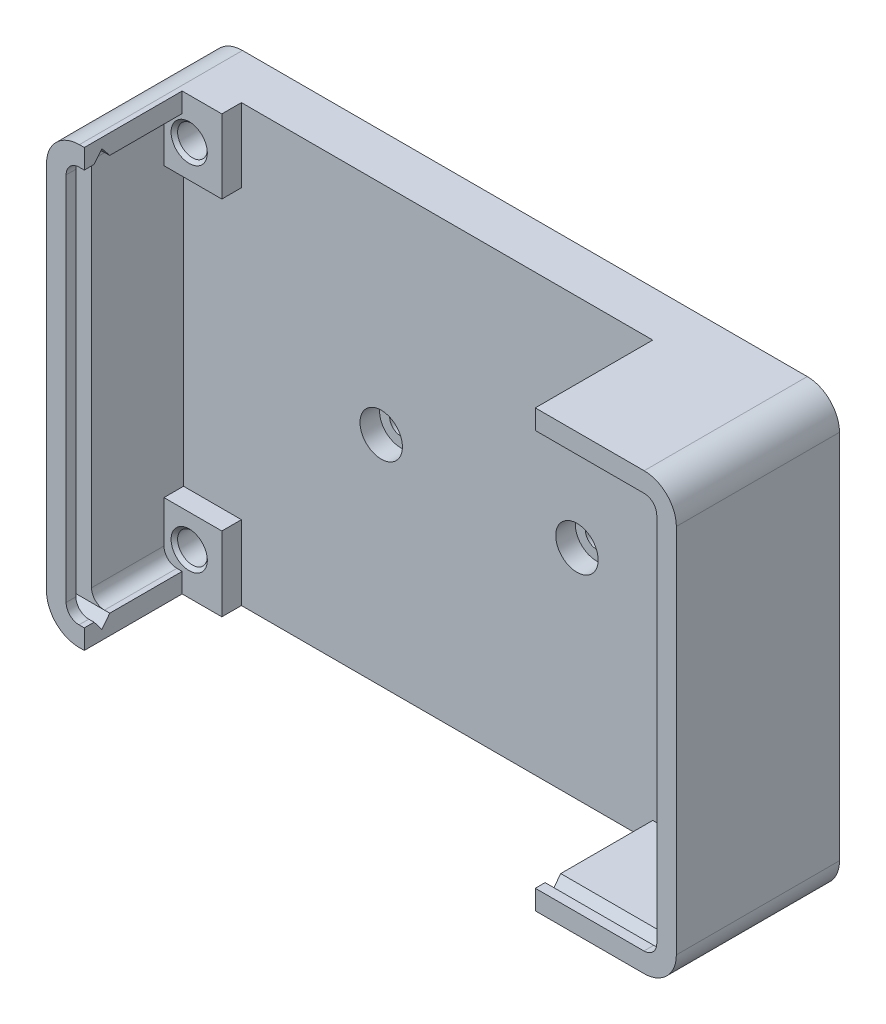
SolidWorks part; units mm, degrees
note: The reader was unsure of these and kept them because the rebuilt part matched: shared geometry of "Sketch1<4>".
ref_plane "Front Plane" through (0, 0, 0) normal (0, 0, 1) x (1, 0, 0)
ref_plane "Top Plane" through (0, 0, 0) normal (0, 1, 0) x (1, 0, 0)
ref_plane "Right Plane" through (0, 0, 0) normal (1, 0, 0) x (0, 0, -1)
sketch "Sketch1" plane through (0, 0, -11.1517) normal (0, 0, -1) x (-1, 0, 0)
  line L0 (-25.2167, 125.2267) -> (-25.2167, 68.4777)
  line L1 (-22.2167, 125.2267) -> (-22.2167, 68.4777)
  line L26 (-27.2482, 127.2583) -> (-113.8062, 127.2583)
  line L28 (-27.2482, 130.2583) -> (-113.8062, 130.2583)
  line L29 (-118.7416, 125.3228) -> (-118.7416, 68.4638)
  line L30 (-113.7774, 63.4996) -> (-27.1948, 63.4996)
  line L39 (-115.7416, 125.3228) -> (-115.7416, 68.4638)
  line L40 (-113.7774, 66.4996) -> (-27.1948, 66.4996)
  line L42 (-22.2167, 68.4777) -> (-22.2167, 125.2267) construction
  line L43 (-25.2167, 68.4777) -> (-25.2167, 125.2267) construction
  arc A20 (-113.8062, 127.2583) -> (-115.7416, 125.3228) centre (-113.8062, 125.3228) ccw
  arc A21 (-113.8062, 130.2583) -> (-118.7416, 125.3228) centre (-113.8062, 125.3228) ccw
  arc A22 (-118.7416, 68.4638) -> (-113.7774, 63.4996) centre (-113.7774, 68.4638) ccw
  arc A23 (-27.1948, 63.4996) -> (-22.2167, 68.4777) centre (-27.1948, 68.4777) ccw
  arc A28 (-27.1948, 66.4996) -> (-25.2167, 68.4777) centre (-27.1948, 68.4777) ccw
  arc A29 (-25.2167, 125.2267) -> (-27.2482, 127.2583) centre (-27.2482, 125.2267) ccw
  arc A31 (-115.7416, 68.4638) -> (-113.7774, 66.4996) centre (-113.7774, 68.4638) ccw
  arc A32 (-22.2167, 125.2267) -> (-27.2482, 130.2583) centre (-27.2482, 125.2267) ccw
  dimension "D2" = 3
  dimension "D3" = 0.3
  dimension "D1" = 0.3
extrude "Boss-Extrude1" add sketch "Sketch1" against normal blind 7
extrude "Boss-Extrude2" add sketch "Sketch1<4>" against normal blind 25
sketch "Sketch1<4>" plane through (0, 0, -11.1517) normal (0, 0, -1) x (-1, 0, 0) same geometry as "Sketch1"
sketch "Sketch2" plane through (0, 0, -4.1517) normal (0, 0, 1) x (1, 0, 0)
  circle A0 centre (111.633, 123.952) radius 2.275
  circle A1 centre (111.633, 69.901) radius 2.275
  circle A2 centre (29.083, 69.901) radius 2.275
  circle A3 centre (29.083, 123.952) radius 2.275
  dimension "D1" = 4.55
extrude "Cut-Extrude1" cut sketch "Sketch2" against normal blind 6
sketch "Sketch3" plane through (0, 0, -4.1517) normal (0, 0, 1) x (1, 0, 0)
  line L0 (70.5272, 127.2583) -> (70.4861, 66.4996) construction
  line L1 (27.2482, 127.2583) -> (113.8062, 127.2583) construction
  line L2 (113.7774, 66.4996) -> (27.1948, 66.4996) construction
  point P1 (85.5067, 96.8789)
  point P8 (70.5067, 96.8789)
  point P9 (55.5067, 96.8992)
  dimension "D1" = 15
hole_wizard "CBORE for M3 SHCS1" positions "Sketch3" profile "Sketch4" counterbore size "M3" standard "ANSI Metric"
sketch "Sketch4" plane through (55.5067, 96.8992, -4.1517) normal (1, 0, 0) x (0, -1, 0)
  line L0 (0, 0) -> (0, 8.0215)
  line L1 (0, 8.0215) -> (1.7, 7)
  line L2 (1.7, 7) -> (1.7, 3)
  line L3 (1.7, 3) -> (3.25, 3)
  line L4 (3.25, 3) -> (3.25, 0)
  line L5 (3.25, 0) -> (0, 0)
  line L10 (0, 8.0215) -> (-1.7, 7) construction
  line L11 (0, -6.35) -> (0, 107.95) construction
  dimension "Hole Dia." = 3.4
  dimension "Hole Depth" = 7
  dimension "C'Bore Dia." = 6.5
  dimension "C'Bore Depth" = 3
  dimension "Drill Angle" = 118
ref_plane "Plane1" through (0, 96.8789, 0) normal (0, -1, 0) x (-1, 0, 0)
sketch "Sketch5" plane through (0, 96.8789, 0) normal (0, -1, 0) x (-1, 0, 0)
  line L0 (-113.7774, -13.8483) -> (-27.1948, -13.8483) construction
  line L1 (-97.1229, -13.8483) -> (-28.0044, -13.8483)
  line L2 (-97.1229, -13.8483) -> (-97.1229, 4.1517)
  line L3 (-97.1229, 4.1517) -> (-28.0044, 4.1517)
  line L4 (-28.0044, -13.8483) -> (-28.0044, 4.1517)
  line L5 (-33.0044, 1.1706) -> (-33.0044, -5.9294) construction
  line L6 (-72.1229, 1.1706) -> (-72.1229, -5.9294) construction
  line L8 (-113.7774, 4.1517) -> (-27.1948, 4.1517) construction
  dimension "D1" = 5
  dimension "D2" = 25
extrude "Cut-Extrude2" cut sketch "Sketch5" against normal through all both and the other way through all
sketch "Sketch6" plane through (22.2167, -0.0074, 0) normal (-1, 0, 0) x (0, 0, 1)
  line L0 (13.8483, 68.4852) -> (13.8483, 125.2341) construction
  line L1 (9.9483, 128.7657) -> (12.3483, 128.7657)
  line L2 (9.9483, 128.7657) -> (9.9483, 64.9536)
  line L3 (9.9483, 64.9536) -> (12.3483, 64.9536)
  line L4 (12.3483, 128.7657) -> (12.3483, 64.9536)
  line L6 (13.8483, 130.2657) -> (-11.1517, 130.2657) construction
  line L7 (9.9483, 127.2657) -> (11.1483, 128.7657)
  line L8 (13.8483, 127.2657) -> (-4.1517, 127.2657) construction
  line L9 (11.1483, 128.7657) -> (12.3483, 127.2657)
  line L10 (12.3483, 66.507) -> (11.1483, 64.9536)
  line L11 (13.8483, 66.507) -> (-4.1517, 66.507) construction
  line L12 (11.1483, 64.9536) -> (9.9483, 66.507)
  point P4 (13.8483, 96.8596)
  point P7 (12.3483, 96.8596)
  dimension "D1" = 1.5
  dimension "D2" = 2.4
  dimension "D3" = 1.5
extrude "Cut-Extrude3" cut sketch "Sketch6" against normal offset from surface (95.025 mm away) 1.5
sketch "Sketch7" plane through (0, 0, -4.1517) normal (0, 0, 1) x (1, 0, 0)
  line L0 (22.2167, 68.4777) -> (22.2167, 125.2267) construction
  line L1 (28.0044, 130.2583) -> (97.1229, 130.2583) construction
  line L2 (27.2482, 130.2583) -> (28.0044, 130.2583) construction
  line L3 (22.2167, 118.952) -> (22.2167, 125.2267)
  line L4 (28.0044, 130.2583) -> (34.083, 130.2583)
  line L5 (27.2482, 130.2583) -> (28.0044, 130.2583)
  line L6 (34.083, 130.2583) -> (34.083, 118.952)
  line L7 (34.083, 118.952) -> (22.2167, 118.952)
  line L8 (118.7416, 125.3228) -> (118.7416, 68.4638) construction
  line L9 (97.1229, 130.2583) -> (113.8062, 130.2583) construction
  line L10 (118.7416, 125.3228) -> (118.7416, 118.952)
  line L11 (106.633, 130.2583) -> (113.8062, 130.2583)
  line L12 (113.7774, 63.4996) -> (97.1229, 63.4996) construction
  line L13 (113.7774, 63.4996) -> (106.633, 63.4996)
  line L14 (28.0044, 63.4996) -> (97.1229, 63.4996) construction
  line L15 (28.0044, 63.4996) -> (27.1948, 63.4996) construction
  line L16 (22.2167, 68.4777) -> (22.2167, 74.901)
  line L17 (28.0044, 63.4996) -> (34.083, 63.4996)
  line L18 (28.0044, 63.4996) -> (27.1948, 63.4996)
  line L19 (34.083, 63.4996) -> (34.083, 74.901)
  line L20 (34.083, 74.901) -> (22.2167, 74.901)
  line L21 (106.633, 130.2583) -> (106.633, 118.952)
  line L22 (106.633, 118.952) -> (118.7416, 118.952)
  line L23 (118.7416, 74.901) -> (106.633, 74.901)
  line L24 (106.633, 74.901) -> (106.633, 63.4996)
  line L25 (118.7416, 74.901) -> (118.7416, 68.4638)
  line L26 (22.2167, 118.952) -> (22.2167, 125.2267)
  circle A0 centre (29.083, 123.952) radius 2.275 construction
  circle A1 centre (29.083, 123.952) radius 2.275
  arc A2 (27.2482, 130.2583) -> (22.2167, 125.2267) centre (27.2482, 125.2267) ccw construction
  arc A3 (27.2482, 130.2583) -> (22.2167, 125.2267) centre (27.2482, 125.2267) ccw
  circle A4 centre (111.633, 123.952) radius 2.275 construction
  circle A5 centre (111.633, 123.952) radius 2.275
  arc A6 (118.7416, 125.3228) -> (113.8062, 130.2583) centre (113.8062, 125.3228) ccw construction
  arc A7 (118.7416, 125.3228) -> (113.8062, 130.2583) centre (113.8062, 125.3228) ccw
  arc A8 (113.7774, 63.4996) -> (118.7416, 68.4638) centre (113.7774, 68.4638) ccw construction
  circle A9 centre (111.633, 69.901) radius 2.275 construction
  arc A10 (113.7774, 63.4996) -> (118.7416, 68.4638) centre (113.7774, 68.4638) ccw
  circle A11 centre (111.633, 69.901) radius 2.275
  arc A12 (22.2167, 68.4777) -> (27.1948, 63.4996) centre (27.1948, 68.4777) ccw construction
  arc A13 (22.2167, 68.4777) -> (27.1948, 63.4996) centre (27.1948, 68.4777) ccw
  circle A14 centre (29.083, 69.901) radius 2.275 construction
  circle A15 centre (29.083, 69.901) radius 2.275
  circle M9 centre (29.083, 69.901) radius 2.275
  circle M10 centre (29.083, 123.952) radius 2.275
  line M11 (27.1948, 66.4996) -> (28.0044, 66.4996)
  line M12 (28.0044, 66.4996) -> (28.0044, 63.4996)
  line M13 (28.0044, 63.4996) -> (97.1229, 63.4996)
  line M15 (97.1229, 66.4996) -> (113.7774, 66.4996)
  arc M16 (113.7774, 66.4996) -> (115.7416, 68.4638) centre (113.7774, 68.4638) ccw
  line M17 (115.7416, 68.4638) -> (115.7416, 125.3228)
  arc M18 (115.7416, 125.3228) -> (113.8062, 127.2583) centre (113.8062, 125.3228) ccw
  line M19 (113.8062, 127.2583) -> (97.1229, 127.2583)
  line M21 (97.1229, 130.2583) -> (28.0044, 130.2583)
  line M22 (28.0044, 130.2583) -> (28.0044, 127.2583)
  line M23 (28.0044, 127.2583) -> (27.2482, 127.2583)
  arc M24 (27.2482, 127.2583) -> (25.2167, 125.2267) centre (27.2482, 125.2267) ccw
  line M25 (25.2167, 125.2267) -> (25.2167, 68.4777)
  arc M26 (25.2167, 68.4777) -> (27.1948, 66.4996) centre (27.1948, 68.4777) ccw
  circle M28 centre (111.633, 123.952) radius 2.275
  circle M29 centre (111.633, 69.901) radius 2.275
  dimension "D1" = 5
  dimension "D2" = 5
  dimension "D3" = 5
  dimension "D4" = 5
  dimension "D5" = 5
  dimension "D6" = 5
  dimension "D7" = 5
extrude "Boss-Extrude3" add sketch "Sketch7" along normal up to surface (3 mm away) contours L7 L6 M21 M22 M23 M24 M25 M10 | L19 L20 M25 M26 M11 M12 M13 M9 | L21 L22 M17 M18 M19 M28 | L23 L24 M15 M16 M17 M29
chamfer "Chamfer1" distance 0.5 angle 45 4 edges at (26.808, 69.901, -1.1517) (109.358, 123.952, -1.1517) (109.358, 69.901, -1.1517) (26.808, 123.952, -1.1517)
equation "\"D3@Sketch7\"=\"D1@Sketch7\""
equation "\"D4@Sketch7\"=\"D1@Sketch7\""
equation "\"D5@Sketch7\"=\"D1@Sketch7\""
equation "\"D6@Sketch7\"=\"D1@Sketch7\""
equation "\"D7@Sketch7\"=\"D1@Sketch7\""
